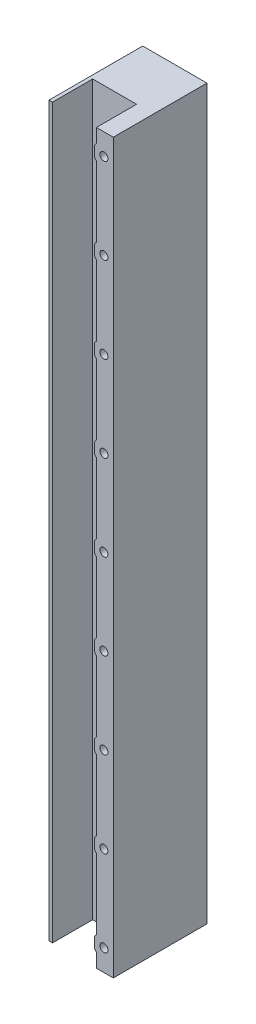
SolidWorks part; units mm, degrees
ref_plane "Top" through (0, 0, 0) normal (0, 0, 1) x (1, 0, 0)
ref_plane "Front" through (0, 0, 0) normal (0, 1, 0) x (1, 0, 0)
ref_plane "Right" through (0, 0, 0) normal (1, 0, 0) x (0, 0, -1)
sketch "Profile Sketch" plane through (0.0456, 0, -0.0242) normal (0, 1, 0) x (-1, 0, 0)
  line L1 (12.0456, 0.0242) -> (0.0456, 0.0242)
  line L2 (0.0456, 0.0242) -> (0.0456, -17.4758)
  line L3 (0.0456, -17.4758) -> (12.0456, -17.4758)
  line L5 (12.0456, -17.4758) -> (12.0456, 0.0242)
  line L12 (12.0456, 0.3949) -> (12.0456, 1.3939) construction
  line L13 (1.7956, 0.0242) -> (1.7956, 4.0449) construction
  dimension "D2" = 1.75
  dimension "Reel Width" = 12
  dimension "Height" = 17.5
extrude "Profile Extrude" add sketch "Profile Sketch" along normal blind 136
sketch "Pocket Sketch" plane through (0, 0, 0) normal (0, 1, 0) x (1, 0, 0)
  line L0 (-1.75, 0) -> (-1.75, -2.6213) construction
  line L2 (-12, 0) -> (0, 0) construction
  line L4 (-11.35, 0) -> (-3.15, 0)
  line L5 (-11.35, 0) -> (-11.35, 7.5)
  line L6 (-11.35, 7.5) -> (-3.15, 7.5)
  line L7 (-3.15, 0) -> (-3.15, 7.5)
  point P9 (-7.25, 0)
  dimension "D1" = 1.75
  dimension "Width" = 8.2
  dimension "Depth" = 7.5
  dimension "Center From Pins" = 5.5
extrude "Pocket Cut" cut sketch "Pocket Sketch" along normal through all
sketch "Index Hole Sketch" plane through (0, 0, 0) normal (0, 0, 1) x (1, 0, 0)
  circle A0 centre (-1.75, 4) radius 0.75
  dimension "D2" = 1.5
  dimension "D3" = 4
  dimension "D1" = 1.75
extrude "First Index Hole Cut" cut sketch "Index Hole Sketch" against normal blind 8
sketch "Index Hole Reinforcement Sketch" plane through (0, 0, 0) normal (0, 0, 1) x (1, 0, 0)
  line L0 (-3.5, 4.9682) -> (-3.5, 3.0318)
  line L1 (-3.15, 5.4283) -> (-3.15, 2.5717)
  line L2 (-3.15, 136) -> (-3.15, 0) construction
  arc A0 (-3.15, 5.4283) -> (-3.5, 4.9682) centre (-1.75, 4) ccw
  arc A1 (-3.5, 3.0318) -> (-3.15, 2.5717) centre (-1.75, 4) ccw
  dimension "D1" = 2
  dimension "D2" = 1.75
extrude "Index Hole Reinforcement" add sketch "Index Hole Reinforcement Sketch" against normal up to next
pattern_linear "Index Hole Pattern" count 9 spacing 16 along (0, 1, 0) of "First Index Hole Cut", "Index Hole Reinforcement"
ref_plane "Mid Plane" through (0, 68, 0) normal (0, -1, 0) x (-1, 0, 0)
equation "\"D2@Index Hole Sketch\"=1.50mm"
